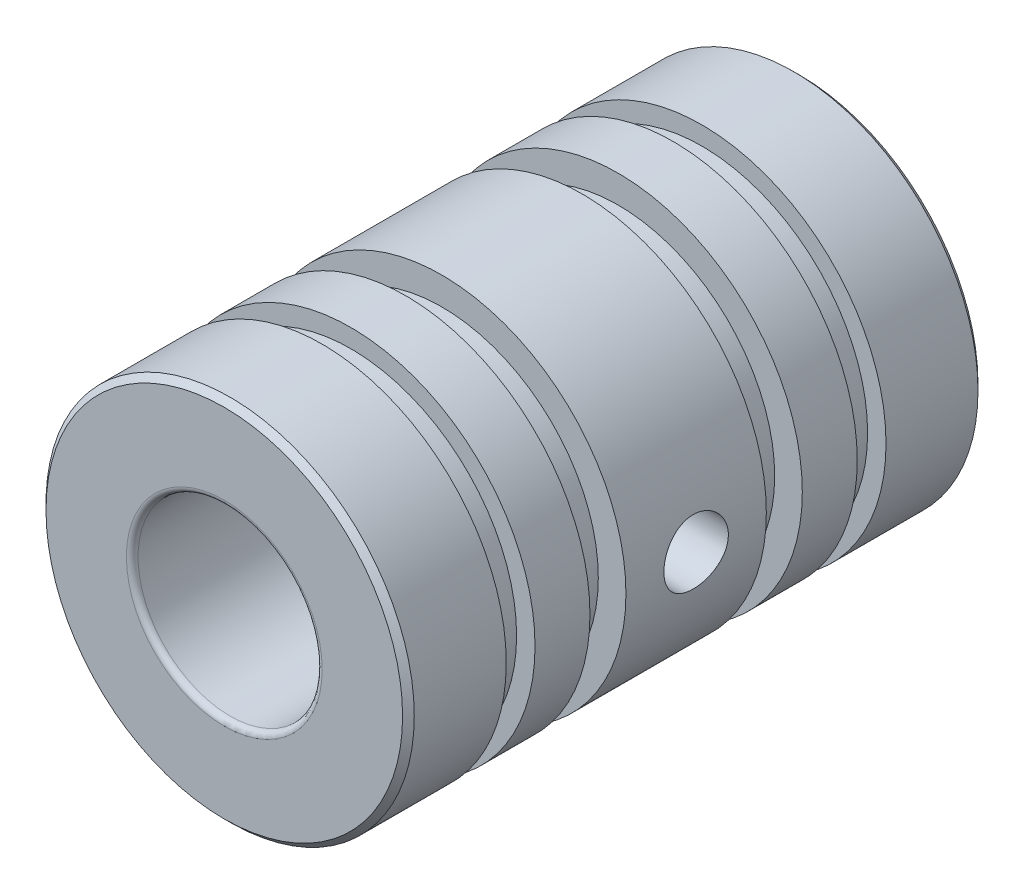
SolidWorks part; units mm, degrees
ref_plane "Front" through (0, 0, 0) normal (0, 0, 1) x (1, 0, 0)
ref_plane "Top" through (0, 0, 0) normal (0, 1, 0) x (1, 0, 0)
ref_plane "Right" through (0, 0, 0) normal (1, 0, 0) x (0, 0, -1)
sketch "Sketch1" plane through (0, 0, 0) normal (1, 0, 0) x (0, 0, -1)
  line L0 (-12.5, 0) -> (12.5, 0)
  line L1 (-12.5, 0) -> (-12.5, -8)
  line L2 (0, 0) -> (0, -8) construction
  line L3 (-12.5, -8) -> (-8.25, -8)
  line L4 (-8.25, -8) -> (-8.25, -7.2)
  line L5 (-8.25, -7.2) -> (-7, -7.2)
  line L6 (-7, -7.2) -> (-7, -8)
  line L7 (-12.5, -8) -> (-12.5, 8) construction
  line L8 (7, -8) -> (-7, -8)
  line L9 (12.5, -13.2503) -> (12.5, 13.2503) construction
  line L10 (-8.25, -8) -> (8.25, -8) construction
  line L16 (7, -7.2) -> (7, -8)
  line L17 (8.25, -7.2) -> (7, -7.2)
  line L18 (8.25, -8) -> (8.25, -7.2)
  line L19 (12.5, -8) -> (8.25, -8)
  line L20 (12.5, 0) -> (12.5, -8)
  line L26 (-12.5, 8) -> (12.5, 8) construction
  point P13 (12.5, 8)
  dimension "D1" = 0.8
  dimension "D4" = 1.25
revolve "Bearing" add sketch "Sketch1" angle 360 mid plane about L0
sketch "Sketch2" plane through (0, 0, 0) normal (0, 0, 1) x (1, 0, 0)
  circle A0 centre (0, 0) radius 4
  circle A1 centre (0, 0) radius 8 construction
  circle A3 centre (0, 0) radius 8 construction
  dimension "For Shaft Dia" = 8
  dimension "OD" = 16
extrude "Bore" cut sketch "Sketch2" against normal through all and the other way through all
sketch "Retaining Hole" plane through (0, 0, 0) normal (1, 0, 0) x (0, 0, -1)
  circle A0 centre (0, 0) radius 1.4
  dimension "Supplier H Hole Dia" = 2.8
extrude "Retaining Hole " cut sketch "Retaining Hole" along normal through all
fillet "ID Fillet" radius 0.254 2 edges at (4, 0, -12.5) (4, 0, 12.5)
chamfer "OD Chamfer" distance 0.254 angle 45 2 edges at (8, 0, -12.5) (8, 0, 12.5)
sketch "O-Rings" plane through (0, 0, 0) normal (1, 0, 0) x (0, 0, -1)
  line L0 (3.05, -8) -> (-3.05, -8) construction
  line L1 (-4.6125, -8) -> (-3.05, -8)
  line L2 (-4.6125, -8) -> (-4.6125, -6.8)
  line L3 (-4.6125, -6.8) -> (-3.05, -6.8)
  line L4 (-3.05, -8) -> (-3.05, -6.8)
  line L5 (3.05, -8) -> (4.6125, -8)
  line L6 (3.05, -8) -> (3.05, -6.8)
  line L7 (3.05, -6.8) -> (4.6125, -6.8)
  line L8 (4.6125, -8) -> (4.6125, -6.8)
  dimension "D1" = 1.5625
  dimension "D2" = 1.2
revolve "O-Rings " cut sketch "O-Rings" angle 360 mid plane about L0
ref_axis "Center Axis 1" through (0, 0, 22.7013) along (0, 0, -1)
ref_plane "Contact Plane 1" through (0, 0, 12.5) normal (0, 0, 1) x (1, 0, 0)
ref_plane "Contact Plane 2" through (0, 0, -12.5) normal (0, 0, -1) x (-1, 0, 0)
equation "\"D1@Sketch1\" = \"OD A@Sketch1\" * .05"
equation "\"D1@O-Rings\" = \"D4@Sketch1\" * 1.25"
equation "\"D2@O-Rings\" = \"D1@Sketch1\" * 1.5"
